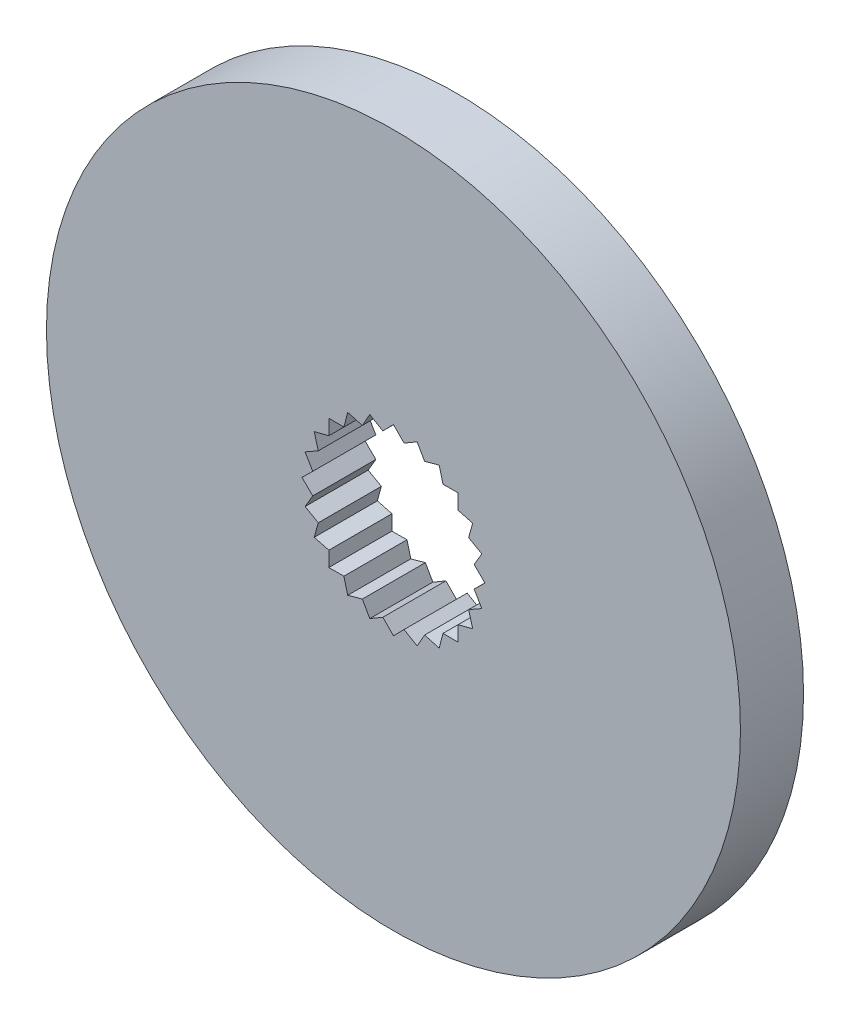
SolidWorks part; units mm, degrees
material "Acrylic (Medium-high impact)"
ref_plane "Front Plane" through (0, 0, 0) normal (0, 0, 1) x (1, 0, 0)
ref_plane "Top Plane" through (0, 0, 0) normal (0, 1, 0) x (1, 0, 0)
ref_plane "Right Plane" through (0, 0, 0) normal (1, 0, 0) x (0, 0, -1)
sketch "Sketch1" plane through (0, 0, 0) normal (0, 0, 1) x (1, 0, 0)
  line L0 (0.7506, 2.8012) -> (0.3368, 2.5579)
  line L1 (0.9873, 2.3836) -> (0.7506, 2.8012)
  line L2 (1.45, 2.5115) -> (0.9873, 2.3836)
  line L3 (1.5706, 2.0469) -> (1.45, 2.5115)
  line L4 (2.0506, 2.0506) -> (1.5706, 2.0469)
  line L5 (2.0469, 1.5706) -> (2.0506, 2.0506)
  line L6 (2.5115, 1.45) -> (2.0469, 1.5706)
  line L7 (2.3836, 0.9873) -> (2.5115, 1.45)
  line L8 (2.8012, 0.7506) -> (2.3836, 0.9873)
  line L9 (2.5579, 0.3368) -> (2.8012, 0.7506)
  line L10 (0, 2.9) -> (-0.3368, 2.5579)
  line L11 (0.3368, 2.5579) -> (0, 2.9)
  line L12 (2.9, 0) -> (2.5579, 0.3368)
  line L13 (2.5579, -0.3368) -> (2.9, 0)
  line L14 (2.8012, -0.7506) -> (2.5579, -0.3368)
  line L15 (2.3836, -0.9873) -> (2.8012, -0.7506)
  line L16 (2.5115, -1.45) -> (2.3836, -0.9873)
  line L17 (2.0469, -1.5706) -> (2.5115, -1.45)
  line L18 (2.0506, -2.0506) -> (2.0469, -1.5706)
  line L19 (1.5706, -2.0469) -> (2.0506, -2.0506)
  line L20 (1.45, -2.5115) -> (1.5706, -2.0469)
  line L21 (0.9873, -2.3836) -> (1.45, -2.5115)
  line L22 (0.7506, -2.8012) -> (0.9873, -2.3836)
  line L23 (0.3368, -2.5579) -> (0.7506, -2.8012)
  line L24 (0, -2.9) -> (0.3368, -2.5579)
  line L25 (-0.3368, -2.5579) -> (0, -2.9)
  line L26 (-0.7506, -2.8012) -> (-0.3368, -2.5579)
  line L27 (-0.9873, -2.3836) -> (-0.7506, -2.8012)
  line L28 (-1.45, -2.5115) -> (-0.9873, -2.3836)
  line L29 (-1.5706, -2.0469) -> (-1.45, -2.5115)
  line L30 (-2.0506, -2.0506) -> (-1.5706, -2.0469)
  line L31 (-2.0469, -1.5706) -> (-2.0506, -2.0506)
  line L32 (-2.5115, -1.45) -> (-2.0469, -1.5706)
  line L33 (-2.3836, -0.9873) -> (-2.5115, -1.45)
  line L34 (-2.8012, -0.7506) -> (-2.3836, -0.9873)
  line L35 (-2.5579, -0.3368) -> (-2.8012, -0.7506)
  line L36 (-2.9, 0) -> (-2.5579, -0.3368)
  line L37 (-2.5579, 0.3368) -> (-2.9, 0)
  line L38 (-2.8012, 0.7506) -> (-2.5579, 0.3368)
  line L39 (-2.3836, 0.9873) -> (-2.8012, 0.7506)
  line L40 (-2.5115, 1.45) -> (-2.3836, 0.9873)
  line L41 (-2.0469, 1.5706) -> (-2.5115, 1.45)
  line L42 (-2.0506, 2.0506) -> (-2.0469, 1.5706)
  line L43 (-1.5706, 2.0469) -> (-2.0506, 2.0506)
  line L44 (-1.45, 2.5115) -> (-1.5706, 2.0469)
  line L45 (-0.9873, 2.3836) -> (-1.45, 2.5115)
  line L46 (-0.7506, 2.8012) -> (-0.9873, 2.3836)
  line L47 (-0.3368, 2.5579) -> (-0.7506, 2.8012)
  circle A0 centre (0, 0) radius 11
  point P50 (0, 0)
  point P79 (0, 0)
  dimension "D1" = 22
  dimension "D2" = 0.3368
  dimension "D3" = 2.9
  dimension "D4" = 2.5579
  dimension "D5" = 24
extrude "Boss-Extrude1" add sketch "Sketch1" along normal blind 2
